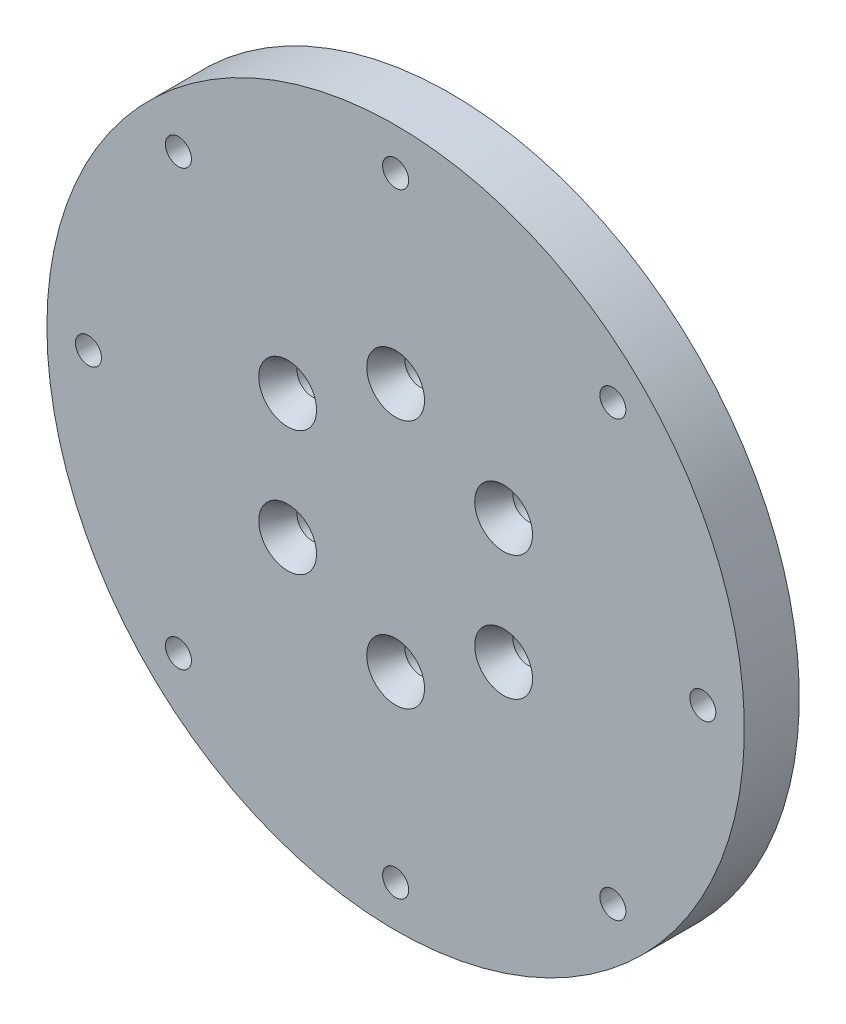
SolidWorks part; units mm, degrees
ref_plane "前视基准面" through (0, 0, 0) normal (0, 0, 1) x (1, 0, 0)
ref_plane "上视基准面" through (0, 0, 0) normal (0, 1, 0) x (1, 0, 0)
ref_plane "右视基准面" through (0, 0, 0) normal (1, 0, 0) x (0, 0, -1)
other "Configuration Table"
sketch "草图1" plane through (0, 0, 0) normal (0, 0, 1) x (1, 0, 0)
  circle A0 centre (0, 0) radius 29.5
  dimension "D1" = 59
extrude "凸台-拉伸1" add sketch "草图1" along normal blind 12
sketch "草图2" plane through (0, 0, 12) normal (0, 0, 1) x (1, 0, 0)
  circle A0 centre (0, 0) radius 48.25
  dimension "D1" = 96.5
extrude "凸台-拉伸2" add sketch "草图2" along normal blind 7.6
fillet "圆角1" radius 5 1 edges at (29.5, 0, 12)
sketch "草图4" plane through (0, 0, 12) normal (0, 0, -1) x (-1, 0, 0)
  circle A0 centre (0, 0) radius 42.5 construction
  circle A1 centre (0, 42.5) radius 3
  circle A2 centre (30.052, 30.052) radius 3
  circle A3 centre (42.5, 0) radius 3
  circle A4 centre (30.052, -30.052) radius 3
  circle A5 centre (0, -42.5) radius 3
  circle A6 centre (-30.052, -30.052) radius 3
  circle A7 centre (-42.5, 0) radius 3
  circle A8 centre (-30.052, 30.052) radius 3
  point P22 (0, 0)
  dimension "D1" = 85
  dimension "D2" = 6
  dimension "D3" = 8
extrude "切除-拉伸1" cut sketch "草图4" against normal blind 3.6
sketch "草图5" plane through (0, 0, 19.6) normal (0, 0, 1) x (1, 0, 0)
  circle A0 centre (0, 0) radius 17.25
  circle A1 centre (0, 17.25) radius 2.1
  circle A2 centre (14.9389, 8.625) radius 2.1
  circle A3 centre (14.9389, -8.625) radius 2.1
  circle A4 centre (0, -17.25) radius 2.1
  circle A5 centre (-14.9389, -8.625) radius 2.1
  circle A6 centre (-14.9389, 8.625) radius 2.1
  point P18 (0, 0)
  dimension "D1" = 34.5
  dimension "D2" = 4.2
  dimension "D3" = 6
extrude "切除-拉伸2" cut sketch "草图5" against normal blind 45.6 contours A0 A1 | A0 A1 | A0 A6 | A0 A6 | A0 A5 | A0 A5 | A0 A4 | A0 A4 | A0 A3 | A0 A3 | A0 A2 | A0 A2 region at (14.1475, 8.1681, 19.6) region at (15.6905, 9.0589, 19.6) region at (15.6905, -9.0589, 19.6) region at (14.1475, -8.1681, 19.6) region at (0, 16.3361, 19.6) region at (0, 18.1178, 19.6) region at (0, -18.1178, 19.6) region at (0, -16.3361, 19.6) region at (-14.1475, 8.1681, 19.6) region at (-15.6905, 9.0589, 19.6) region at (-15.6905, -9.0589, 19.6) region at (-14.1475, -8.1681, 19.6)
ref_axis "基准轴1" through (14.9389, 8.625, 0) along (0, 0, 1)
ref_axis "基准轴2" through (0, 17.25, 0) along (0, 0, 1)
ref_plane "基准面1" through (7.4695, 12.9375, 0) normal (0.5, 0.866, 0) x (0.866, -0.5, 0)
sketch "草图6" plane through (7.4695, 12.9375, 0) normal (0.5, 0.866, 0) x (0.866, -0.5, 0)
  line L0 (6.525, -19.6) -> (10.725, -19.6) construction
  line L1 (6.525, -19.6) -> (10.725, -19.6)
  line L2 (8.625, -19.6) -> (12.625, -19.6)
  line L3 (-48.25, -19.6) -> (48.25, -19.6) construction
  line L4 (8.625, -16.2) -> (10.725, -16.2)
  line L5 (8.625, 0) -> (8.625, -19.6) construction
  line L6 (10.725, -16.2) -> (12.625, -19.6)
  line L7 (8.625, -16.2) -> (8.625, -19.6)
  dimension "D1" = 4
  dimension "D2" = 3.4
  dimension "D3" = 2.1
revolve "切除-旋转1" cut sketch "草图6" angle 360 about axis through (14.9389, 8.625, 0) along (0, 0, 1) region at (16.3023, 7.8378, 18.0765)
pattern_circular "阵列(圆周)1" count 6 every 60 about axis through (0, 0, 19.6) along (0, 0, 1) of "切除-旋转1"
sketch "草图7" plane through (0, 0, 15.6) normal (0, 0, -1) x (-1, 0, 0)
  circle A0 centre (0, 42.5) radius 3 construction
  circle A1 centre (0, 0) radius 48.25
  circle A2 centre (0, 0) radius 48.25
  circle A3 centre (0, 42.5) radius 3
  circle A4 centre (0, 42.5) radius 1.8
  circle A5 centre (30.052, 30.052) radius 1.8
  circle A6 centre (42.5, 0) radius 1.8
  circle A7 centre (30.052, -30.052) radius 1.8
  circle A8 centre (0, -42.5) radius 1.8
  circle A9 centre (-30.052, -30.052) radius 1.8
  circle A10 centre (-42.5, 0) radius 1.8
  circle A11 centre (-30.052, 30.052) radius 1.8
  point P24 (0, 0)
  dimension "D2" = 3.6
  dimension "D1" = 0
  dimension "D3" = 8
extrude "切除-拉伸3" cut sketch "草图7" against normal blind 45.6 contours A4 | A11 | A10 | A9 | A8 | A7 | A6 | A5 region at (0, 42.5, 15.6) region at (-30.052, 30.052, 15.6) region at (-42.5, 0, 15.6) region at (-30.052, -30.052, 15.6) region at (0, -42.5, 15.6) region at (30.052, -30.052, 15.6) region at (42.5, 0, 15.6) region at (30.052, 30.052, 15.6)
